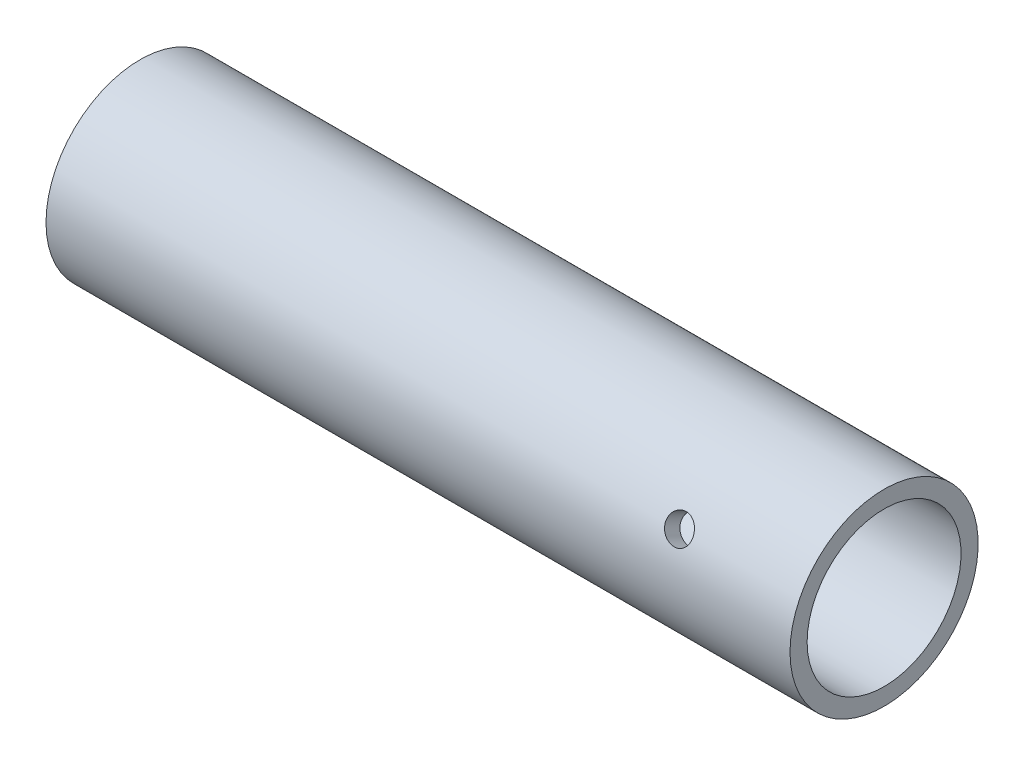
SolidWorks part; units mm, degrees
ref_plane "Front Plane" through (0, 0, 0) normal (0, 0, 1) x (1, 0, 0)
ref_plane "Top Plane" through (0, 0, 0) normal (0, 1, 0) x (1, 0, 0)
ref_plane "Right Plane" through (0, 0, 0) normal (1, 0, 0) x (0, 0, -1)
sketch "Sketch3" plane through (0, 0, 0) normal (0, 0, 1) x (1, 0, 0)
  line L0 (-58.5481, 189.9573) -> (284.033, 189.9573) construction
  line L2 (213.4012, -189.6279) -> (558.7345, -189.6279) construction
  line L4 (263.0584, -148.5737) -> (308.4812, -148.5737) construction
  line L42 (295.0584, -144.0737) -> (305.0584, -144.0737)
  line L43 (305.0584, -144.0737) -> (305.0584, -143.0737)
  line L45 (261.5584, -143.0737) -> (305.0584, -143.0737)
  line L55 (261.5584, -144.3237) -> (261.5584, -148.0737)
  line L63 (263.0584, -148.0737) -> (263.0584, -144.5737)
  line L64 (263.0584, -148.0737) -> (261.5584, -148.0737)
  line L65 (263.0584, -144.5737) -> (295.0584, -144.5737)
  line L66 (295.0584, -144.5737) -> (295.0584, -144.0737)
  line L97 (261.5584, -144.3237) -> (261.5584, -143.0737)
  dimension "D2" = 1.5
  dimension "D3" = 1
  dimension "D4" = 1
  dimension "D5" = 4
  dimension "D6" = 4.5
  dimension "D7" = 10
  dimension "D10" = 43.5
revolve "Revolve19" add sketch "Sketch3" angle 360 about L4 region at (280.3466, -143.9859, 0)
ref_plane "Plane1" through (0, -26.4476, -53.8513) normal (0, 0.4408, 0.8976) x (1, 0, 0)
sketch "Sketch4" plane through (0, -26.4476, -53.8513) normal (0, 0.4408, 0.8976) x (1, 0, 0)
  circle A0 centre (298.0243, -133.3586) radius 0.8
  dimension "D1" = 1.6
extrude "Cut-Extrude1" cut sketch "Sketch4" against normal through all
ref_axis "Axis1" through (298.0243, -146.9265, 3.354) along (0, 0.4408, 0.8976)
ref_plane "Plane8" through (0, -31.2967, -63.7249) normal (0, 0.4408, 0.8976) x (1, 0, 0)
